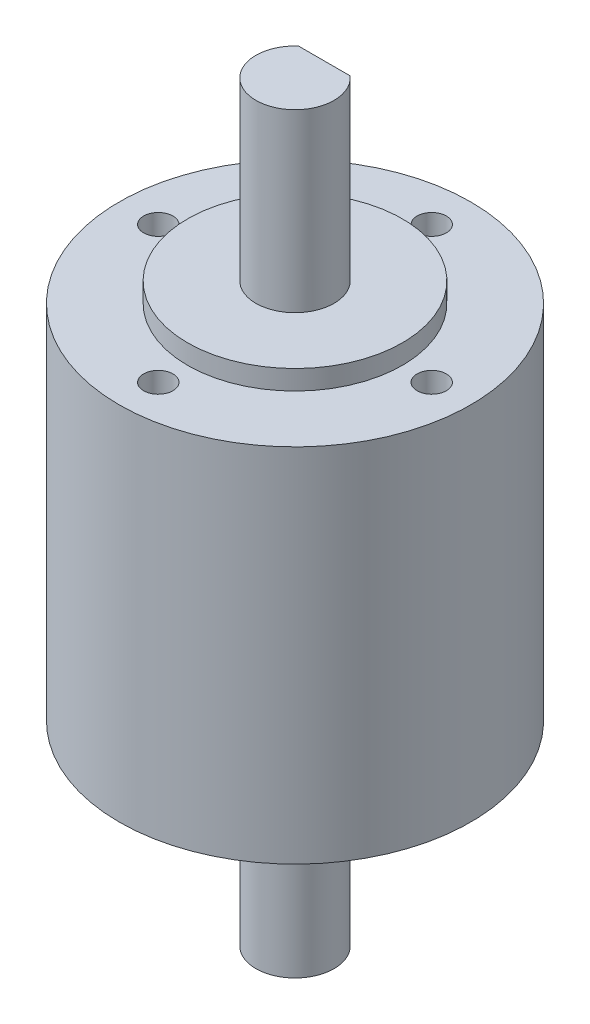
SolidWorks part; units mm, degrees
ref_plane "Front Plane" through (0, 0, 0) normal (0, 0, 1) x (1, 0, 0)
ref_plane "Top Plane" through (0, 0, 0) normal (0, 1, 0) x (1, 0, 0)
ref_plane "Right Plane" through (0, 0, 0) normal (1, 0, 0) x (0, 0, -1)
sketch "Sketch1" plane through (0, 0, 0) normal (0, 1, 0) x (1, 0, 0)
  circle A0 centre (0, 0) radius 18
  dimension "D1" = 36
extrude "Boss-Extrude1" add sketch "Sketch1" along normal mid plane 37
sketch "Sketch2" plane through (0, 18.5, 0) normal (0, 1, 0) x (1, 0, 0)
  circle A0 centre (0, 0) radius 11
  dimension "D1" = 22
extrude "Boss-Extrude2" add sketch "Sketch2" along normal blind 2
sketch "Sketch3" plane through (0, 20.5, 0) normal (0, 1, 0) x (1, 0, 0)
  circle A0 centre (0, 0) radius 4
  dimension "D1" = 8
extrude "Boss-Extrude4" add sketch "Sketch3" along normal blind 18
sketch "Sketch4" plane through (0, 38.5, 0) normal (0, 1, 0) x (1, 0, 0)
  line L0 (-2.6458, 3) -> (2.6458, 3)
  line L1 (0, -4) -> (0, 3) construction
  arc A0 (0, -4) -> (2.6458, 3) centre (0, 0) ccw construction
  circle A1 centre (0, 0) radius 4
  arc A2 (2.6458, 3) -> (-2.6458, 3) centre (0, 0) ccw
  arc A3 (-2.6458, 3) -> (0, -4) centre (0, 0) ccw construction
  dimension "D2" = 7
  dimension "D1" = 0
extrude "Cut-Extrude1" cut sketch "Sketch4" against normal blind 15
sketch "Sketch5" plane through (0, 18.5, 0) normal (0, 1, 0) x (1, 0, 0)
  circle A0 centre (0, 0) radius 14 construction
  circle A1 centre (0, 14) radius 1.5
  circle A2 centre (-14, 0) radius 1.5
  circle A3 centre (0, -14) radius 1.5
  circle A4 centre (14, 0) radius 1.5
  dimension "D1" = 28
  dimension "D2" = 3
extrude "Cut-Extrude2" cut sketch "Sketch5" against normal blind 4
mirror "Mirror1" about plane through (0, 0, 0) normal (0, 1, 0) of "Cut-Extrude2", "Cut-Extrude1", "Boss-Extrude4", "Boss-Extrude2"
